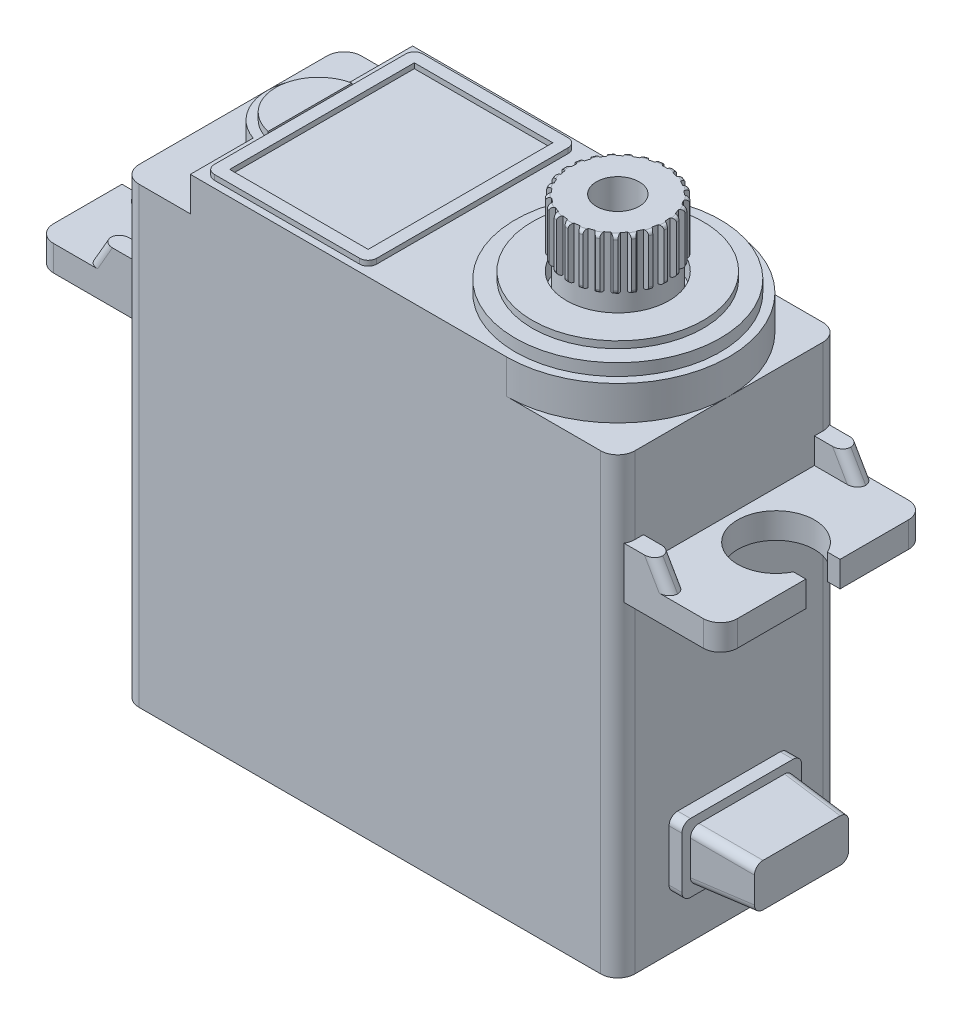
SolidWorks part; units mm, degrees
ref_plane "Front Plane" through (0, 0, 0) normal (0, 0, 1) x (1, 0, 0)
ref_plane "Top Plane" through (0, 0, 0) normal (0, 1, 0) x (1, 0, 0)
ref_plane "Right Plane" through (0, 0, 0) normal (1, 0, 0) x (0, 0, -1)
sketch "Sketch1" plane through (0, 0, 0) normal (0, 1, 0) x (1, 0, 0)
  line L1 (-14.5, 6.5) -> (14.5, 6.5)
  line L2 (-14.5, 6.5) -> (-14.5, -6.5)
  line L3 (-14.5, -6.5) -> (14.5, -6.5)
  line L4 (14.5, 6.5) -> (14.5, -6.5)
  line L5 (-14.5, 6.5) -> (14.5, -6.5) construction
  line L6 (-14.5, -6.5) -> (14.5, 6.5) construction
  point P0 (0, 0)
  dimension "D1" = 13
  dimension "D2" = 29
extrude "Boss-Extrude1" add sketch "Sketch1" along normal blind 28.5
sketch "Sketch3" plane through (-14.5, 0, 0) normal (-1, 0, 0) x (0, 0, 1)
  line L0 (6.5, 28.5) -> (6.5, 0) construction
  line L1 (6.5, 20.5) -> (-6.5, 20.5)
  line L2 (6.5, 20.5) -> (6.5, 19)
  line L3 (6.5, 19) -> (-6.5, 19)
  line L4 (-6.5, 20.5) -> (-6.5, 19)
  line L5 (-6.5, 28.5) -> (-6.5, 0) construction
  line L6 (-6.5, 0) -> (6.5, 0) construction
  dimension "D1" = 1.5
  dimension "D2" = 19
extrude "Boss-Extrude2" add sketch "Sketch3" along normal blind 5.5
sketch "Sketch4" plane through (-14.5, 0, 0) normal (-1, 0, 0) x (0, 0, 1)
  line L0 (6.5, 28.5) -> (6.5, 20.5) construction
  line L1 (-6.5, 20.5) -> (6.5, 20.5)
  line L2 (-6.5, 20.5) -> (-6.5, 22)
  line L3 (-6.5, 22) -> (6.5, 22)
  line L4 (6.5, 20.5) -> (6.5, 22)
  line L6 (-5.5, 22) -> (5.5, 22)
  line L7 (-5.5, 22) -> (-5.5, 20.5)
  line L8 (-5.5, 20.5) -> (5.5, 20.5)
  line L9 (5.5, 22) -> (5.5, 20.5)
  line M5 (-6.5, 20.5) -> (6.5, 20.5)
  line M6 (6.5, 20.5) -> (6.5, 28.5)
  line M8 (-6.5, 28.5) -> (-6.5, 20.5)
  dimension "D1" = 1.5
  dimension "D2" = 1
  dimension "D3" = 1
extrude "Boss-Extrude3" add sketch "Sketch4" along normal blind 2.5 contours L7 L3 M8 M5 | L3 L9 M5 M6
sketch "Sketch6" plane through (0, 28.5, 0) normal (0, 1, 0) x (1, 0, 0)
  line L0 (14.5, 6.5) -> (-14.5, 6.5) construction
  line L1 (-14.5, -6.5) -> (-10.5, -6.5)
  line L2 (-14.5, -6.5) -> (-14.5, 6.5)
  line L3 (-14.5, 6.5) -> (-10.5, 6.5)
  line L4 (-10.5, -6.5) -> (-10.5, 6.5)
  line L5 (-9.5, 6.5) -> (-9.5, -6.5) construction
  line L6 (-14.5, -6.5) -> (14.5, -6.5) construction
  circle A0 centre (-9.5, 0) radius 3
  line M4 (-14.5, -6.5) -> (14.5, -6.5)
  line M6 (14.5, 6.5) -> (-14.5, 6.5)
  line M7 (-14.5, 6.5) -> (-14.5, -6.5)
  dimension "D3" = 6
  dimension "D1" = 4
  dimension "D2" = 1
extrude "Cut-Extrude2" cut sketch "Sketch6" against normal blind 2 contours A0 L4 M6 M7 M4
mirror "Mirror1" about plane through (0, 0, 0) normal (1, 0, 0) of "Boss-Extrude2", "Boss-Extrude3"
sketch "Sketch5" plane through (0, 28.5, 0) normal (0, 1, 0) x (1, 0, 0)
  line L1 (1.5, 6.5) -> (14.5, 6.5)
  line L2 (1.5, 6.5) -> (1.5, -6.5)
  line L3 (1.5, -6.5) -> (14.5, -6.5)
  line L4 (14.5, 6.5) -> (14.5, -6.5)
  line L5 (1.5, 6.5) -> (14.5, -6.5) construction
  line L6 (1.5, -6.5) -> (14.5, 6.5) construction
  circle A0 centre (8, 0) radius 6.5
  line M2 (14.5, -6.5) -> (14.5, 6.5)
  line M3 (14.5, 6.5) -> (-10.5, 6.5)
extrude "Cut-Extrude1" cut sketch "Sketch5" against normal blind 2 contours A0 L4 M3 | A0 L3 M2
sketch "Sketch7" plane through (0, 28.5, 0) normal (0, 1, 0) x (1, 0, 0)
  line L0 (14.5, 0) -> (8, 0) construction
  arc A0 (8, -6.5) -> (8, 6.5) centre (8, 0) ccw construction
  circle A1 centre (8, 0) radius 6
  circle A2 centre (8, 0) radius 3
  dimension "D1" = 12
  dimension "D2" = 6
extrude "Boss-Extrude4" add sketch "Sketch7" along normal blind 0.7
sketch "Sketch8" plane through (0, 29.2, 0) normal (0, 1, 0) x (1, 0, 0)
  circle A0 centre (8, 0) radius 5
  circle A1 centre (8, 0) radius 3
  dimension "D1" = 10
extrude "Boss-Extrude5" add sketch "Sketch8" along normal blind 0.4
sketch "Sketch9" plane through (0, 28.5, 0) normal (0, 1, 0) x (1, 0, 0)
  line L0 (8, 0) -> (-12.5, 0) construction
  line L1 (8, 6.5) -> (-10.5, 6.5) construction
  line L2 (-1, -6.1) -> (-9.5, -6.1)
  line L3 (-0.5, -5.6) -> (-0.5, 5.6)
  line L4 (-1, 6.1) -> (-9.5, 6.1)
  line L5 (-10, -5.6) -> (-10, 5.6)
  line L6 (-0.5, -6.1) -> (-10, 6.1) construction
  line L7 (-0.5, 6.1) -> (-10, -6.1) construction
  line L8 (-10.5, -6.5) -> (-10.5, -2.8284) construction
  line L9 (-1.2, 5.4) -> (-9.3, 5.4)
  line L10 (-9.3, -5.4) -> (-9.3, 5.4)
  line L11 (-1.2, -5.4) -> (-9.3, -5.4)
  line L12 (-1.2, -5.4) -> (-1.2, 5.4)
  line L13 (-0.5, -6.1) -> (-10, -6.1) construction
  line L14 (-10, -6.1) -> (-10, 6.1) construction
  line L15 (-0.5, -6.1) -> (-0.5, 6.1) construction
  line L16 (-0.5, 6.1) -> (-10, 6.1) construction
  arc A0 (-10.5, 2.8284) -> (-10.5, -2.8284) centre (-9.5, 0) ccw construction
  arc A1 (-9.5, -6.1) -> (-10, -5.6) centre (-9.5, -5.6) cw
  arc A2 (-1, -6.1) -> (-0.5, -5.6) centre (-1, -5.6) ccw
  arc A3 (-0.5, 5.6) -> (-1, 6.1) centre (-1, 5.6) ccw
  arc A4 (-9.5, 6.1) -> (-10, 5.6) centre (-9.5, 5.6) ccw
  point P6 (-5.25, 0)
  dimension "D5" = 0.5
  dimension "D1" = 0.4
  dimension "D2" = 9.5
  dimension "D3" = 0.5
  dimension "D4" = 0.7
extrude "Boss-Extrude6" add sketch "Sketch9" along normal blind 0.3
sketch "Sketch10" plane through (0, 28.5, 0) normal (0, 1, 0) x (1, 0, 0)
  circle A0 centre (-9.5, 0) radius 3
  circle A1 centre (-9.5, 0) radius 2.5
  line M11 (-10, -5.6) -> (-10, 5.6)
  dimension "D1" = 5
extrude "Boss-Extrude7" add sketch "Sketch10" along normal blind 0.4 contours A1 M11
sketch "Sketch11" plane through (0, 28.5, 0) normal (0, 1, 0) x (1, 0, 0)
  line L0 (8, -3) -> (8, 3) construction
  circle A0 centre (8, 0) radius 3 construction
  circle A1 centre (8, 0) radius 2.75
  circle A2 centre (8, 0) radius 1.25
  dimension "D1" = 5.5
  dimension "D2" = 2.5
extrude "Boss-Extrude8" add sketch "Sketch11" along normal blind 5
sketch "Sketch12" plane through (0, 33.5, 0) normal (0, 1, 0) x (1, 0, 0)
  line L0 (8, 0) -> (8, -3.25) construction
  line L1 (8, -3.25) -> (7.6429, -2.3159)
  line L2 (7.6429, -2.3159) -> (8.3571, -2.3159)
  line L3 (8, -3.25) -> (8.3571, -2.3159)
  circle A0 centre (8, 0) radius 2.9994
  point P6 (8, -2.3159)
  circle M4 centre (8, 0) radius 2.75
  dimension "D1" = 3.25
  dimension "D2" = 1
extrude "Boss-Extrude9" add sketch "Sketch12" against normal blind 3 contours L0 L1 A0 M4 | L0 A0 L3 M4
sketch "Sketch13" plane through (0, 0, 0) normal (0, 0, 1) x (1, 0, 0)
  line L0 (8, 33.5) -> (8, 29.6) construction
  line L1 (10.75, 33.5) -> (5.25, 33.5) construction
  line L2 (13, 29.6) -> (3, 29.6) construction
pattern_circular "CirPattern1" count 25 over 360 about axis through (8, 0, 0) along (0, 1, 0) of "Boss-Extrude9"
fillet "Fillet1" radius 0.2 50 edges at (5.0065, 30.5, 0.1883) (5.2861, 30.5, -1.2771) (5.0538, 30.5, -0.562) (5.6889, 30.5, -1.9119) (6.237, 30.5, -2.4265) (6.8959, 30.5, -2.7887) (10.3111, 30.5, -1.9119) (9.763, 30.5, -2.4265) (7.6241, 30.5, -2.9757) (8.3759, 30.5, -2.9757) (9.1041, 30.5, -2.7887) (10.5325, 33.5, 1.6071) (10.8526, 33.5, 0.9269) (10.0532, 33.5, 2.1864) (9.445, 33.5, 2.6284) (8.7459, 33.5, 2.9051) (8, 33.5, 2.9994) (8, 30.5, 2.9994) (7.2541, 33.5, 2.9051) (6.555, 33.5, 2.6284) (5.9468, 33.5, 2.1864) (5.4675, 33.5, 1.6071) (5.1474, 33.5, 0.9269) (5.0065, 33.5, 0.1883) (5.0538, 33.5, -0.562) (5.2861, 33.5, -1.2771) (5.6889, 33.5, -1.9119) (6.237, 33.5, -2.4265) (6.8959, 33.5, -2.7887) (7.6241, 33.5, -2.9757) (8.3759, 33.5, -2.9757) (9.1041, 33.5, -2.7887) (10.9935, 33.5, 0.1883) (10.9462, 33.5, -0.562) (10.7139, 33.5, -1.2771) (10.3111, 33.5, -1.9119) (9.763, 33.5, -2.4265) (10.8526, 30.5, 0.9269) (10.9935, 30.5, 0.1883) (10.9462, 30.5, -0.562) (10.7139, 30.5, -1.2771) (10.0532, 30.5, 2.1864) (10.5325, 30.5, 1.6071) (9.445, 30.5, 2.6284) (8.7459, 30.5, 2.9051) (7.2541, 30.5, 2.9051) (6.555, 30.5, 2.6284) (5.9468, 30.5, 2.1864) (5.1474, 30.5, 0.9269) (5.4675, 30.5, 1.6071)
sketch "Sketch14" plane through (0, 20.5, 0) normal (0, 1, 0) x (1, 0, 0)
  line L0 (20, -6.5) -> (20, 6.5) construction
  line L1 (19.5, 0) -> (21.0511, 0) construction
  line L3 (20, -1) -> (19.5, -1)
  line L4 (20, -1) -> (20, 1)
  line L5 (20, 1) -> (19.5, 1)
  line L6 (19.5, -1) -> (19.5, 1)
  line L7 (20, -1) -> (19.5, 1) construction
  line L8 (20, 1) -> (19.5, -1) construction
  line L9 (19, 1) -> (20, 1)
  line L10 (19, 1) -> (19, -1)
  line L11 (19, -1) -> (20, -1)
  line L12 (20, 1) -> (20, -1)
  line L13 (19, 1) -> (20, -1) construction
  line L14 (19, -1) -> (20, 1) construction
  circle A0 centre (17.254, 0) radius 2.25
  point P7 (19.75, 0)
  line M8 (20, -6.5) -> (20, 6.5)
  dimension "D1" = 4.5
  dimension "D2" = 1
  dimension "D3" = 0.5
extrude "Cut-Extrude3" cut sketch "Sketch14" against normal blind 10 contours L9 A0 L11 L10 | L11 A0 L6 L9 L10 | A0 L6 L3 L5 M8 | A0 L6 L9 | A0 L11 L6 | L6 A0
mirror "Mirror2" about plane through (0, 0, 0) normal (1, 0, 0) of "Cut-Extrude3"
sketch "Sketch15" plane through (-20, 0, 0) normal (-1, 0, 0) x (0, 0, 1)
  line L1 (6.5, 19) -> (6, 19)
  line L2 (6.5, 19) -> (6.5, 22)
  line L3 (6.5, 22) -> (6, 22)
  line L4 (6, 19) -> (6, 22)
  dimension "D1" = 0.5
  dimension "D2" = 3
extrude "Cut-Extrude4" cut sketch "Sketch15" against normal blind 5.5
sketch "Sketch16" plane through (-14.5, 0, 0) normal (-1, 0, 0) x (0, 0, 1)
  line L0 (5.5, 20.5) -> (-5.5, 20.5) construction
  line L1 (5.5, 22) -> (5, 22)
  line L2 (5.5, 22) -> (5.5, 20.5)
  line L3 (5.5, 20.5) -> (5, 20.5)
  line L4 (5, 22) -> (5, 20.5)
  dimension "D1" = 0.5
extrude "Boss-Extrude10" add sketch "Sketch16" along normal blind 2.5
mirror "Mirror3" about plane through (0, 0, 0) normal (0, 0, 1) of "Cut-Extrude4", "Boss-Extrude10"
mirror "Mirror4" about plane through (0, 0, 0) normal (1, 0, 0) of "Mirror3", "Cut-Extrude4", "Boss-Extrude10"
fillet "Fillet2" radius 1 8 edges at (14.5, 13.25, -6.5) (14.5, 13.25, 6.5) (-14.5, 13.25, -6.5) (-14.5, 13.25, 6.5) (20, 19.75, -6) (20, 19.75, 6) (-20, 19.75, 6) (-20, 19.75, -6)
chamfer "Chamfer1" distance 1.5 angle 30 4 edges at (17, 22, 5.5) (17, 22, -5.5) (-17, 22, 5.5) (-17, 22, -5.5)
fillet "Fillet3" radius 0.5 8 edges at (-16.567, 21.25, -5) (-16.567, 21.25, 5) (-16.567, 21.25, 6) (16.567, 21.25, -6) (16.567, 21.25, -5) (16.567, 21.25, 6) (16.567, 21.25, 5) (-16.567, 21.25, -6)
sketch "Sketch17" plane through (14.5, 0, 0) normal (1, 0, 0) x (0, 0, -1)
  line L0 (0, 19) -> (0, 5) construction
  line L1 (5.5, 19) -> (-5.5, 19) construction
  line L3 (-3, 7) -> (3, 7)
  line L4 (-3.5, 6.5) -> (-3.5, 3.5)
  line L5 (-3, 3) -> (3, 3)
  line L6 (3.5, 6.5) -> (3.5, 3.5)
  line L7 (-3.5, 7) -> (3.5, 3) construction
  line L8 (-3.5, 3) -> (3.5, 7) construction
  arc A0 (-3.5, 3.5) -> (-3, 3) centre (-3, 3.5) ccw
  arc A1 (3, 3) -> (3.5, 3.5) centre (3, 3.5) ccw
  arc A2 (3, 7) -> (3.5, 6.5) centre (3, 6.5) cw
  arc A3 (-3, 7) -> (-3.5, 6.5) centre (-3, 6.5) ccw
  dimension "D4" = 0.5
  dimension "D1" = 14
  dimension "D2" = 7
  dimension "D3" = 4
extrude "Boss-Extrude11" add sketch "Sketch17" along normal blind 0.75
sketch "Sketch18" plane through (15.25, 0, 0) normal (1, 0, 0) x (0, 0, -1)
  line L0 (-3.5, 5) -> (3.5, 5) construction
  line L1 (-3.5, 6.5) -> (-3.5, 3.5) construction
  line L2 (3.5, 3.5) -> (3.5, 6.5) construction
  line L4 (-3, 6.5) -> (3, 6.5)
  line L5 (-3, 6.5) -> (-3, 3.5)
  line L6 (-3, 3.5) -> (3, 3.5)
  line L7 (3, 6.5) -> (3, 3.5)
  line L8 (-3, 6.5) -> (3, 3.5) construction
  line L9 (-3, 3.5) -> (3, 6.5) construction
  point P6 (0, 5)
  dimension "D1" = 6
  dimension "D2" = 3
extrude "Boss-Extrude12" add sketch "Sketch18" along normal blind 3.5
chamfer "Chamfer2" distance 3.5 angle 4 4 edges at (18.75, 5, 3) (18.75, 3.5, 0) (18.75, 5, -3) (18.75, 6.5, 0)
fillet "Fillet4" radius 0.5 4 edges at (17, 6.3776, -2.8776) (17, 3.6224, 2.8776) (17, 6.3776, 2.8776) (17, 3.6224, -2.8776)
